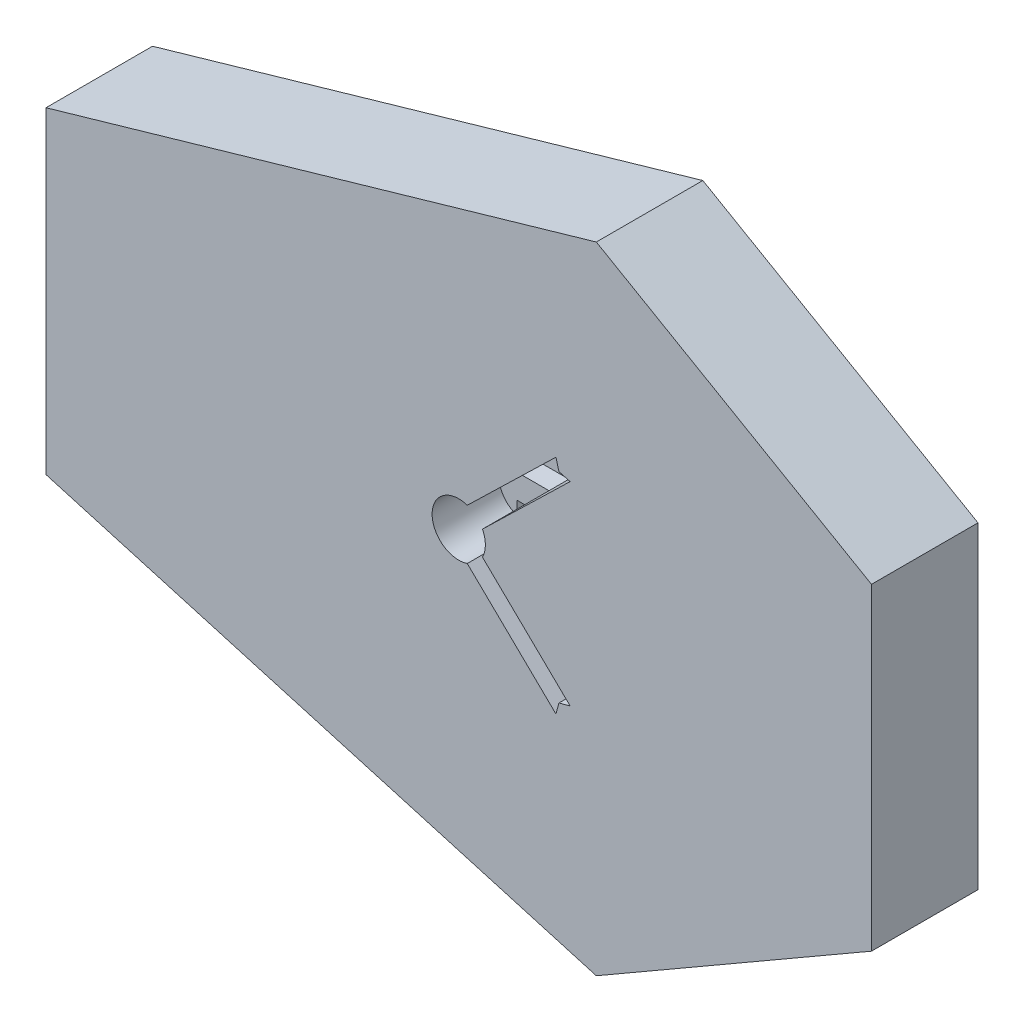
SolidWorks part; units mm, degrees
ref_plane "Front Plane" through (0, 0, 0) normal (0, 0, 1) x (1, 0, 0)
ref_plane "Top Plane" through (0, 0, 0) normal (0, 1, 0) x (1, 0, 0)
ref_plane "Right Plane" through (0, 0, 0) normal (1, 0, 0) x (0, 0, -1)
sketch "Sketch2" plane through (0, 0, 0) normal (0, 0, 1) x (1, 0, 0)
  line L0 (-36.15, 11.9319) -> (-36.15, -11.9319) construction
  line L1 (5.1833, -23.8638) -> (-36.15, -11.9319) construction
  line L2 (5.1833, -23.8638) -> (25.85, -11.9319) construction
  line L3 (25.85, -11.9319) -> (25.85, 11.9319) construction
  line L4 (25.85, 11.9319) -> (5.1833, 23.8638) construction
  line L5 (-36.15, 11.9319) -> (5.1833, 23.8638) construction
  line L6 (-36.15, 11.9319) -> (-36.15, -11.9319)
  line L7 (5.1833, -23.8638) -> (-36.15, -11.9319)
  line L8 (5.1833, -23.8638) -> (25.85, -11.9319)
  line L9 (25.85, -11.9319) -> (25.85, 11.9319)
  line L10 (25.85, 11.9319) -> (5.1833, 23.8638)
  line L11 (-36.15, 11.9319) -> (5.1833, 23.8638)
  line L12 (-34.65, -3.7) -> (-33.15, -3.7) construction
  line L13 (-33.15, -3.7) -> (-33.15, -1.5) construction
  line L14 (-33.15, -1.5) -> (-34.65, -1.5) construction
  line L15 (-34.65, -1.5) -> (-34.65, -3.7) construction
  line L16 (-34.65, 1.5) -> (-33.15, 1.5) construction
  line L17 (-33.15, 1.5) -> (-33.15, 3.7) construction
  line L18 (-33.15, 3.7) -> (-34.65, 3.7) construction
  line L19 (-34.65, 3.7) -> (-34.65, 1.5) construction
  line L20 (-34.65, -3.7) -> (-33.15, -3.7)
  line L21 (-33.15, -3.7) -> (-33.15, -1.5)
  line L22 (-33.15, -1.5) -> (-34.65, -1.5)
  line L23 (-34.65, -1.5) -> (-34.65, -3.7)
  line L24 (-34.65, 1.5) -> (-33.15, 1.5)
  line L25 (-33.15, 1.5) -> (-33.15, 3.7)
  line L26 (-33.15, 3.7) -> (-34.65, 3.7)
  line L27 (-34.65, 3.7) -> (-34.65, 1.5)
extrude "Boss-Extrude1" add sketch "Sketch2" along normal blind 1.5
sketch "Sketch4" plane through (0, 0, 1.5) normal (0, 0, 1) x (1, 0, 0)
  line L6 (5.1833, 23.8638) -> (-36.15, 11.9319)
  line L7 (-36.15, 11.9319) -> (-36.15, -11.9319)
  line L8 (-36.15, -11.9319) -> (5.1833, -23.8638)
  line L9 (5.1833, -23.8638) -> (25.85, -11.9319)
  line L10 (25.85, -11.9319) -> (25.85, 11.9319)
  line L11 (25.85, 11.9319) -> (5.1833, 23.8638)
  line L12 (5.1833, 23.8638) -> (-36.15, 11.9319)
  line L13 (-36.15, 11.9319) -> (-36.15, -11.9319)
  line L14 (-36.15, -11.9319) -> (5.1833, -23.8638)
  line L15 (5.1833, -23.8638) -> (25.85, -11.9319)
  line L16 (25.85, -11.9319) -> (25.85, 11.9319)
  line L17 (25.85, 11.9319) -> (5.1833, 23.8638)
  circle A0 centre (-5.15, 0) radius 2
  point P9 (-5.15, 0)
  dimension "D2" = 4
  dimension "D1" = 0
extrude "Boss-Extrude2" add sketch "Sketch4" along normal blind 6.5
sketch "Sketch5" plane through (0, 0, 8) normal (0, 0, 1) x (1, 0, 0)
  line L0 (-12.6753, 7.5253) -> (-19.0706, 5.7908) construction
  line L1 (-19.0706, 5.7908) -> (-18.2853, 2.8954) construction
  line L2 (-10.2301, 5.0801) -> (-18.2853, 2.8954) construction
  line L3 (-8.0454, 13.1353) -> (-10.2301, 5.0801) construction
  line L4 (-10.9408, 13.9206) -> (-8.0454, 13.1353) construction
  line L5 (-10.9408, 13.9206) -> (-12.6753, 7.5253) construction
  line L6 (-12.6753, 7.5253) -> (-19.0706, 5.7908) construction
  line L7 (-19.0706, 5.7908) -> (-18.2853, 2.8954) construction
  line L8 (-10.2301, 5.0801) -> (-18.2853, 2.8954) construction
  line L9 (-8.0454, 13.1353) -> (-10.2301, 5.0801) construction
  line L10 (-10.9408, 13.9206) -> (-8.0454, 13.1353) construction
  line L11 (-10.9408, 13.9206) -> (-12.6753, 7.5253) construction
  line L12 (-6.9303, 0.9114) -> (-13.5171, 7.297) construction
  line L13 (-13.5171, 7.297) -> (-12.6753, 7.5253) construction
  line L14 (-12.451, 8.3523) -> (-5.7901, 1.8948) construction
  line L15 (-12.6753, 7.5253) -> (-12.451, 8.3523) construction
  line L16 (-6.4, 3.7) -> (-3.9, -3.7) construction
  line L17 (-5.15, 0) -> (-5.15, 20.8808) construction
  line L18 (-12.451, 8.3523) -> (-13.5171, 7.297) construction
  line L19 (-12.9841, 7.8246) -> (-12.6753, 7.5253) construction
  line L20 (-6.9303, 0.9114) -> (-4.5099, 0.9114) construction
  line L21 (-4.5099, 0.9114) -> (-4.5099, 1.8948) construction
  line L22 (-4.5099, 1.8948) -> (-5.7901, 1.8948)
  line L23 (5.1833, 23.8638) -> (-36.15, 11.9319) construction
  line L24 (2.6841, 7.8246) -> (2.3753, 7.5253) construction
  line L25 (2.151, 8.3523) -> (3.2171, 7.297) construction
  line L26 (0.6408, 13.9206) -> (2.3753, 7.5253) construction
  line L27 (0.6408, 13.9206) -> (-2.2546, 13.1353) construction
  line L28 (-2.2546, 13.1353) -> (-0.0699, 5.0801) construction
  line L29 (-0.0699, 5.0801) -> (7.9853, 2.8954) construction
  line L30 (8.7706, 5.7908) -> (7.9853, 2.8954) construction
  line L31 (2.3753, 7.5253) -> (8.7706, 5.7908) construction
  line L32 (-5.7901, 0.9114) -> (-5.7901, 1.8948)
  line L33 (-3.3697, 0.9114) -> (-5.7901, 0.9114)
  line L34 (2.3753, 7.5253) -> (2.151, 8.3523)
  line L35 (2.151, 8.3523) -> (-4.5099, 1.8948)
  line L36 (3.2171, 7.297) -> (2.3753, 7.5253)
  line L37 (-3.3697, 0.9114) -> (3.2171, 7.297)
  circle A0 centre (-5.15, 0) radius 2 construction
  point P17 (-5.15, 20.8808)
  dimension "D1" = 1.5
extrude "Cut-Extrude1" cut sketch "Sketch5" against normal up to surface (6.5 mm away) up to face at (-3.15, 0, 1.5)
sketch "Sketch9" plane through (0, 0, 1.5) normal (0, 0, 1) x (1, 0, 0)
  line L8 (2.151, 8.3523) -> (2.3753, 7.5253)
  line L9 (2.3753, 7.5253) -> (3.2171, 7.297)
  line L10 (3.2171, 7.297) -> (1.8203, 5.9429)
  line L11 (-3.3697, 0.9114) -> (3.2171, 7.297) construction
  line L12 (1.8203, 5.9429) -> (0.7764, 7.0196)
  line L13 (2.151, 8.3523) -> (-4.5099, 1.8948) construction
  line L14 (0.7764, 7.0196) -> (2.151, 8.3523)
  dimension "D1" = 1.5
extrude "Cut-Extrude2" cut sketch "Sketch9" against normal through all
sketch "Sketch7" plane through (0, 0, 8) normal (0, 0, 1) x (1, 0, 0)
  line L0 (-7.15, 0) -> (-3.15, 0) construction
  line L1 (-5.15, 2) -> (-5.15, -2) construction
  arc A0 (-4.5099, 1.8948) -> (-3.3697, 0.9114) centre (-5.15, 0) ccw construction
ref_plane "Plane1" through (0, 0, 0) normal (0, -1, 0) x (1, 0, 0)
mirror "Mirror1" about plane through (0, 0, 0) normal (0, -1, 0) of "Cut-Extrude2", "Cut-Extrude1"
sketch "Sketch8" plane through (0, 0, 1.5) normal (0, 0, 1) x (1, 0, 0)
  line L2 (-5.7901, 0.9114) -> (-5.7901, 1.8948) construction
  line L3 (-3.3697, 0.9114) -> (-5.7901, 0.9114) construction
  line L4 (-5.7901, 0.9114) -> (-5.7901, 1.8948)
  line L5 (-3.3697, 0.9114) -> (-5.7901, 0.9114)
  line L6 (-7.15, 0) -> (-3.15, 0) construction
  line L7 (-3.3697, -0.9114) -> (-5.7901, -0.9114)
  line L8 (-5.7901, -0.9114) -> (-5.7901, -1.8948)
  arc A0 (-3.3697, -0.9114) -> (-3.3697, 0.9114) centre (-5.15, 0) ccw construction
  arc A1 (-3.3697, -0.9114) -> (-3.3697, 0.9114) centre (-5.15, 0) ccw
  arc A2 (-4.5099, 1.8948) -> (-4.5099, -1.8948) centre (-5.15, 0) ccw construction
  arc A3 (-5.7901, 1.8948) -> (-5.7901, -1.8948) centre (-5.15, 0) ccw
extrude "Boss-Extrude3" add sketch "Sketch8" along normal blind 1.5
